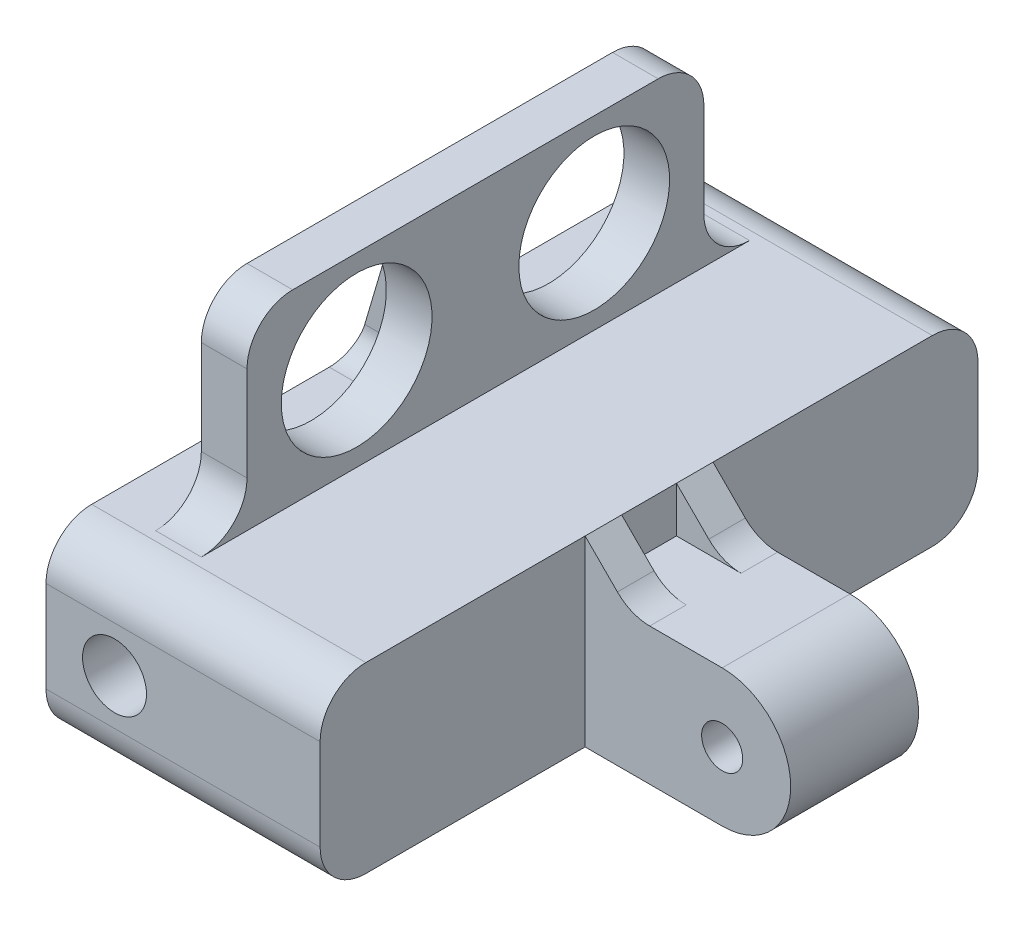
SolidWorks part; units mm, degrees
material "ABS"
ref_plane "Front Plane" through (0, 0, 0) normal (0, 0, 1) x (1, 0, 0)
ref_plane "Top Plane" through (0, 0, 0) normal (0, 1, 0) x (1, 0, 0)
ref_plane "Right Plane" through (0, 0, 0) normal (1, 0, 0) x (0, 0, -1)
sketch "Sketch1" plane through (0, 0, 0) normal (0, 0, 1) x (1, 0, 0)
  line L1 (0, 7.5) -> (-15, 7.5)
  line L3 (0, -7.5) -> (-15, -7.5)
  line L4 (-15, 7.5) -> (-15, -7.5)
  arc A0 (0, -7.5) -> (0, 7.5) centre (0, 0) ccw
  circle A1 centre (0, 0) radius 2.25
  dimension "D1" = 7.5
  dimension "D3" = 4.5
  dimension "D2" = 15
extrude "Boss-Extrude1" add sketch "Sketch1" along normal blind 14
sketch "Sketch2" plane through (-15, 0, 0) normal (-1, 0, 0) x (0, 0, 1)
  line L0 (7, 7.5) -> (7, -7.5) construction
  line L1 (-29, -7.5) -> (43, -7.5)
  line L2 (-29, -7.5) -> (-29, 12.5)
  line L3 (-29, 12.5) -> (43, 12.5)
  line L4 (43, -7.5) -> (43, 12.5)
  line L5 (14, 7.5) -> (0, 7.5) construction
  line L6 (14, -7.5) -> (0, -7.5) construction
  point P8 (7, 12.5)
  dimension "D1" = 20
  dimension "D2" = 72
extrude "Boss-Extrude2" add sketch "Sketch2" along normal blind 30
sketch "Sketch3" plane through (-45, 0, 0) normal (-1, 0, 0) x (0, 0, 1)
  line L0 (-29, 2.5) -> (43, 2.5) construction
  line L1 (-29, 12.5) -> (-29, -7.5) construction
  line L2 (43, -7.5) -> (43, 12.5) construction
  line L3 (-15, 2.5) -> (29, 2.5) construction
  line L4 (43, 12.5) -> (-29, 12.5) construction
  circle A0 centre (-15, 2.5) radius 7
  circle A1 centre (29, 2.5) radius 7
  point P2 (22, 2.5)
  point P14 (7, 2.5)
  point P19 (7, 12.5)
  point P20 (-8, 2.5)
  dimension "D1" = 14
  dimension "D2" = 30
extrude "Cut-Extrude1" cut sketch "Sketch3" against normal blind 15 contours A1 | A0 region at (-45, 2.5, 29)
fillet "Fillet1" radius 5 4 edges at (-30, 12.5, 43) (-30, -7.5, 43) (-30, -7.5, -29) (-30, 12.5, -29)
sketch "Sketch4" plane through (0, 0, 14) normal (0, 0, 1) x (1, 0, 0)
  line L0 (-15, 12.5) -> (-10, 7.5)
  line L1 (0, 7.5) -> (-15, 7.5) construction
  line L2 (-15, 7.5) -> (-15, 12.5) construction
  dimension "D1" = 45
rib "Rib1" sketch "Sketch4" sketch "Sketch4" thickness 4 extrusion direction parallel to sketch draft on no parameters "D1"=4
ref_plane "Plane1" through (0, 0, 7) normal (0, 0, 1) x (1, 0, 0)
mirror "Mirror1" about plane through (0, 0, 7) normal (0, 0, 1) of "Rib1"
fillet "Fillet2" radius 5 2 edges at (-10, 7.5, 2) (-10, 7.5, 12)
sketch "Sketch6" plane through (-45, 0, 0) normal (-1, 0, 0) x (0, 0, 1)
  line L0 (38, 12.5) -> (-24, 12.5) construction
  line L1 (-18, 12.5) -> (32, 12.5)
  line L2 (-18, 12.5) -> (-18, 32.8317)
  line L3 (-18, 32.8317) -> (32, 32.8317)
  line L4 (32, 12.5) -> (32, 32.8317)
  point P6 (7, 12.5)
  point P7 (7, 32.8317)
  dimension "D1" = 50
  dimension "D2" = 20.3317
extrude "Boss-Extrude3" add sketch "Sketch6" against normal blind 5 from offset 6 offset against normal yes
sketch "Sketch7" plane through (-39, 0, 0) normal (-1, 0, 0) x (0, 0, 1)
  line L0 (-6, 22.6658) -> (20, 22.6658) construction
  line L1 (32, 32.8317) -> (-18, 32.8317) construction
  line L2 (32, 12.5) -> (32, 32.8317) construction
  circle A0 centre (-6, 22.6658) radius 8.25
  circle A1 centre (20, 22.6658) radius 8.25
  point P4 (0, 0)
  point P7 (7, 22.6658)
  point P8 (0, 0)
  point P9 (0, 0)
  point P12 (7, 32.8317)
  point P15 (32, 22.6658)
  dimension "D1" = 16.5
  dimension "D2" = 26
extrude "Cut-Extrude2" cut sketch "Sketch7" against normal up to next
fillet "Fillet3" radius 5 2 edges at (-36.5, 12.5, 32) (-36.5, 12.5, -18)
fillet "Fillet4" radius 5 2 edges at (-36.5, 32.8317, 32) (-36.5, 32.8317, -18)
sketch "Sketch8" plane through (0, 0, 7) normal (0, 0, 1) x (1, 0, 0)
  line L0 (-39, 32.8317) -> (-45, 12.5)
rib "Rib2" sketch "Sketch8" sketch "Sketch8" thickness 4 extrusion direction parallel to sketch draft on no parameters "D1"=4
fillet "Fillet5" radius 3 2 edges at (-42, 12.5, 5) (-42, 12.5, 9)
sketch "Sketch9" plane through (-45, 0, 0) normal (-1, 0, 0) x (0, 0, 1)
  line L0 (-10.5, 10.5) -> (24.5, 10.5)
  line L1 (-10.5, -5.5) -> (24.5, -5.5)
  line L2 (9, 32.8317) -> (5, 32.8317) construction
  line L3 (-29, 7.5) -> (-29, -2.5) construction
  arc A0 (-10.5, -5.5) -> (-10.5, 10.5) centre (-10.5, 2.5) ccw
  arc A1 (24.5, 10.5) -> (24.5, -5.5) centre (24.5, 2.5) ccw
  point P8 (0, 0)
  point P9 (0, 0)
  point P10 (0, 0)
  point P11 (0, 0)
  point P14 (7, 32.8317)
  point P15 (7, 10.5)
  point P16 (-29, 2.5)
  point P17 (-2.5, 2.5)
  dimension "D1" = 8
  dimension "D2" = 35
extrude "Cut-Extrude3" cut sketch "Sketch9" against normal blind 20
fillet "Fillet6" radius 2 4 edges at (-35, 10.5, 24.5) (-35, -5.5, 24.5) (-35, -5.5, -10.5) (-35, 10.5, -10.5)
sketch "Sketch10" plane through (0, 0, -29) normal (0, 0, -1) x (-1, 0, 0)
  line L0 (45, 7.5) -> (45, -2.5) construction
  circle A0 centre (37.5, 2.5) radius 3.5
  point P2 (0, 0)
  point P5 (45, 2.5)
  dimension "D2" = 7
  dimension "D1" = 7.5
extrude "Cut-Extrude4" cut sketch "Sketch10" against normal up to next
mirror "Mirror2" about plane through (0, 0, 7) normal (0, 0, 1) of "Cut-Extrude4"
